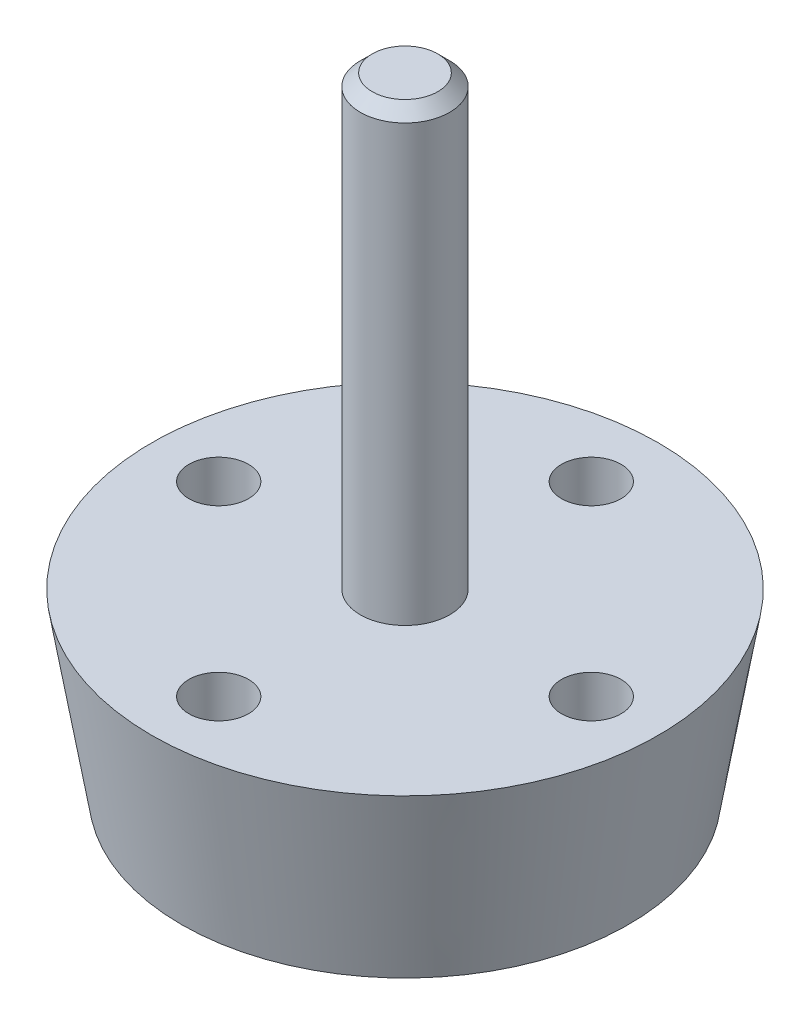
SolidWorks part; units mm, degrees
ref_plane "Front Plane" through (0, 0, 0) normal (0, 0, 1) x (1, 0, 0)
ref_plane "Top Plane" through (0, 0, 0) normal (0, 1, 0) x (1, 0, 0)
ref_plane "Right Plane" through (0, 0, 0) normal (1, 0, 0) x (0, 0, -1)
sketch "Sketch1" plane through (0, 0, 0) normal (0, 1, 0) x (1, 0, 0)
  circle A0 centre (0, 0) radius 7.5
  dimension "D1" = 15
ref_plane "Plane1" through (0, 6, 0) normal (0, 1, 0) x (1, 0, 0)
sketch "Sketch3" plane through (0, 6, 0) normal (0, 1, 0) x (1, 0, 0)
  circle A0 centre (0, 0) radius 8.5
  dimension "D1" = 17
loft "Loft1" add profiles "Sketch3", "Sketch1" connector at (4.7833, 6, 7.0264) connector at (4.4008, 0, 6.0732)
sketch "Sketch4" plane through (0, 6, 0) normal (0, 1, 0) x (1, 0, 0)
  circle A0 centre (0, 0) radius 1.5
  dimension "D1" = 3
extrude "Boss-Extrude1" add sketch "Sketch4" along normal blind 15
sketch "Sketch5" plane through (0, 0, 0) normal (0, -1, 0) x (1, 0, 0)
  circle A0 centre (0, 0) radius 5
  dimension "D1" = 10
extrude "Cut-Extrude1" cut sketch "Sketch5" against normal blind 2
sketch "Sketch6" plane through (0, 0, 0) normal (0, -1, 0) x (1, 0, 0)
  circle A0 centre (0, 6.25) radius 1
  circle A2 centre (6.25, 0) radius 1
  circle A3 centre (0, -6.25) radius 1
  circle A4 centre (-6.25, 0) radius 1
  point P4 (0, 0)
  point P14 (0, 0)
  dimension "D1" = 2
  dimension "D3" = 6.25
  dimension "D2" = 4
extrude "Cut-Extrude4" cut sketch "Sketch6" against normal up to surface (6 mm away) up to face at (0, 6, 1.5)
sketch "Sketch8" plane through (0, 2, 0) normal (0, -1, 0) x (1, 0, 0)
  circle A0 centre (0, 0) radius 1.5
  dimension "D1" = 3
extrude "Cut-Extrude5" cut sketch "Sketch8" against normal blind 1
fillet "Fillet1" radius 1 1 edges at (0, 2, -1.5)
chamfer "Chamfer1" distance 0.4 angle 45 1 edges at (0, 21, 1.5)
